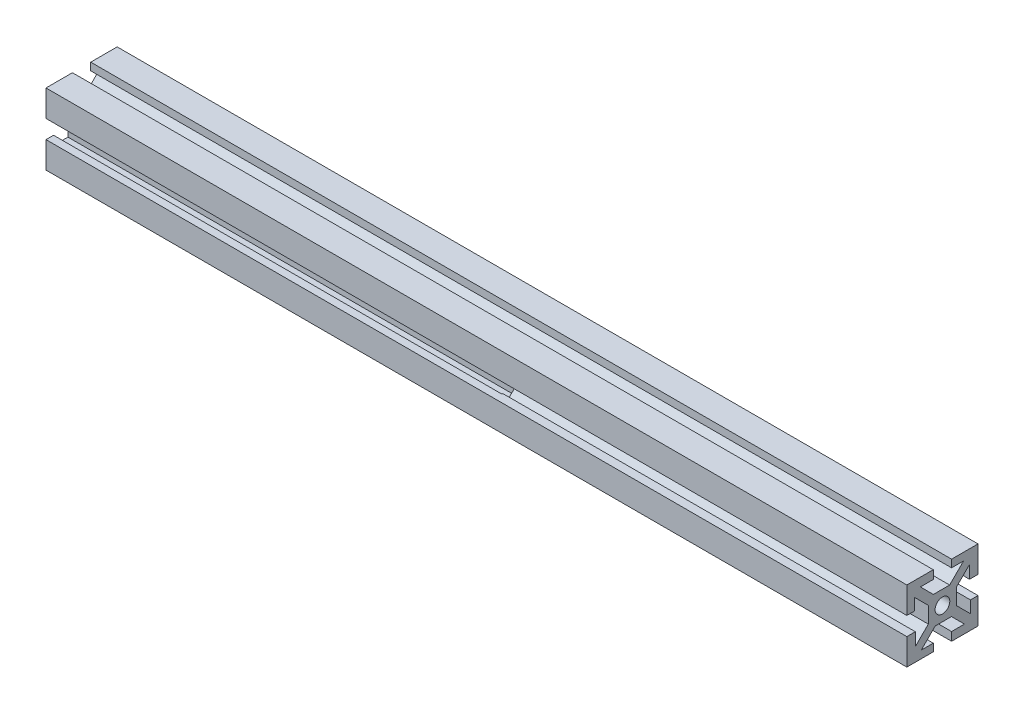
SolidWorks part; units mm, degrees
material "6061 Alloy"
ref_plane "Front Plane" through (0, 0, 0) normal (0, 0, 1) x (1, 0, 0)
ref_plane "Top Plane" through (0, 0, 0) normal (0, 1, 0) x (1, 0, 0)
ref_plane "Right Plane" through (0, 0, 0) normal (1, 0, 0) x (0, 0, -1)
sketch "Sketch1" plane through (0, 0, 0) normal (1, 0, 0) x (0, 0, -1)
  line L0 (2.5534, 5) -> (7.4749, 9.9215)
  line L1 (-5, 5) -> (5, 5)
  line L2 (-5, 5) -> (-5, -5)
  line L3 (-5, -5) -> (5, -5)
  line L4 (5, 5) -> (5, -5)
  line L5 (-5, 5) -> (5, -5) construction
  line L6 (-5, -5) -> (5, 5) construction
  line L7 (7.4749, 9.9215) -> (9.5962, 7.8001)
  line L8 (9.5962, 7.8001) -> (5, 3.2039)
  line L9 (5, 5) -> (13.6489, 13.6489) construction
  line L10 (7.4749, 9.9215) -> (3.24, 9.9215)
  line L11 (3.24, 9.9215) -> (3.24, 12.5962)
  line L12 (3.24, 12.5962) -> (12.5962, 12.5962)
  line L13 (9.5962, 7.8001) -> (9.5962, 3.24)
  line L14 (9.5962, 3.24) -> (12.5962, 3.24)
  line L15 (12.5962, 3.24) -> (12.5962, 12.5962)
  line L17 (0, 0) -> (0, 24.089) construction
  line L18 (0, 0) -> (23.75, 0) construction
  circle A0 centre (0, 0) radius 2.605
  point P0 (0, 0)
  dimension "D1" = 5.21
  dimension "D2" = 10
  dimension "D3" = 10
  dimension "D4" = 3
  dimension "D5" = 1.27
  dimension "D6" = 6.5
  dimension "D7" = 3.24
  dimension "D8" = 3.24
  dimension "D9" = 3
extrude "Boss-Extrude1" add sketch "Sketch1" along normal blind 304.8 contours L4 L1 L2 L3 A0 | L8 L7 L0 L1 L4 | L14 L15 L12 L11 L10 L7 L13 region at (0, 4.8586, -3.7767) region at (0, 6.7479, -6.3823) region at (0, 9.18, -9.3105)
ref_axis "Axis1" through (0, 0, 0) along (1, 0, 0)
pattern_circular "CirPattern1" count 4 over 360 about axis through (0, 0, 0) along (1, 0, 0) of "Boss-Extrude1"
sketch "Sketch2" plane through (0, 0, 12.5962) normal (0, 0, 1) x (1, 0, 0)
  circle A0 centre (152.4, 0) radius 2.78
  dimension "D1" = 5.56
  dimension "D2" = 152.4
extrude "Cut-Extrude1" cut sketch "Sketch2" against normal blind 30
sketch "Sketch3" plane through (0, 0, 0) normal (-1, 0, 0) x (0, 0, 1)
  line L0 (9.9215, 7.4749) -> (9.9215, 3.24) construction
  line L1 (4.8415, 6.35) -> (9.9215, 6.35)
  line L2 (4.8415, 6.35) -> (4.8415, -6.35)
  line L3 (4.8415, -6.35) -> (9.9215, -6.35)
  line L4 (9.9215, 6.35) -> (9.9215, -6.35)
  line L5 (4.8415, 6.35) -> (9.9215, -6.35) construction
  line L6 (4.8415, -6.35) -> (9.9215, 6.35) construction
  point P0 (7.3815, 0)
  dimension "D1" = 12.7
  dimension "D2" = 0
  dimension "D3" = 5.08
  dimension "D4" = 0
extrude "Cut-Extrude2" cut sketch "Sketch3" against normal blind 158.75
